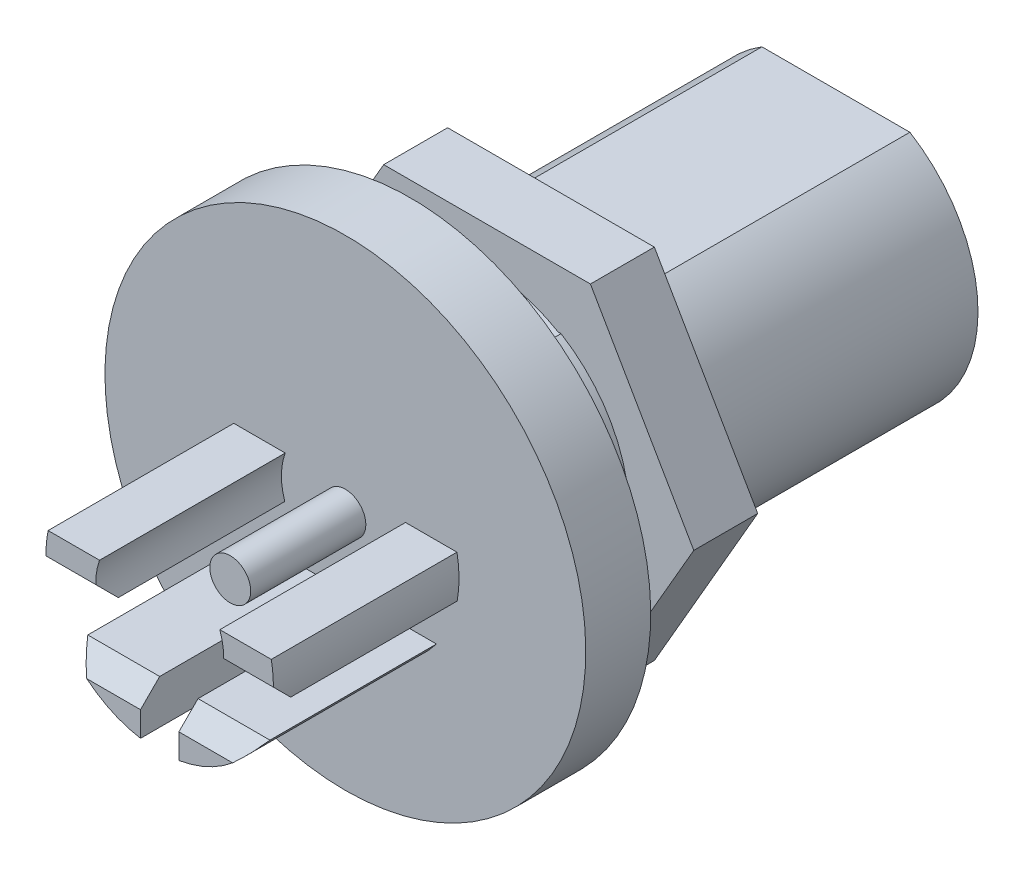
SolidWorks part; units mm, degrees
note: '?' marks a value the reader was unsure of. The reader was unsure of these and kept them because the rebuilt part matched: shared geometry of "Sketch1<3>", "Sketch2<3>".
material "Brass"
ref_plane "Front Plane" through (0, 0, 0) normal (0, 0, 1) x (1, 0, 0)
ref_plane "Top Plane" through (0, 0, 0) normal (0, 1, 0) x (1, 0, 0)
ref_plane "Right Plane" through (0, 0, 0) normal (1, 0, 0) x (0, 0, -1)
ref_axis "Axis1" through (0, 0, -88.99) along (0, 0, 1)?
ref_axis "Axis2" through (0, -55, 0) along (0, 1, 0)?
ref_axis "Axis3" through (-88.99, 0, 0) along (1, 0, 0)?
sketch "Sketch1" plane through (0, 0, 0) normal (1, 0, 0) x (0, 0, -1)
  line L0 (0, 0) -> (5, 0)
  line L1 (5, 0) -> (5, 4)
  line L2 (5, 4) -> (19.18, 4)
  line L3 (19.18, 4) -> (19.18, 5.5562)
  line L4 (19.18, 5.5562) -> (2.54, 5.5562)
  line L5 (2.54, 5.5562) -> (2.54, 6.85)
  line L6 (2.54, 9.4) -> (0, 9.4)
  line L7 (0, 9.4) -> (0, 0)
  line L8 (5, 2) -> (17.18, 2)
  line L9 (17.18, 2) -> (17.18, 0.5)
  line L10 (17.18, 0.5) -> (7, 0.5)
  line L11 (7, 0.5) -> (7, 0)
  line L12 (7, 0) -> (5, 0)
  line L13 (7, 0) -> (19.18, 0) construction
  line L14 (2.54, 8.65) -> (1.71, 8.65)
  line L15 (1.71, 8.65) -> (1.71, 6.85)
  line L16 (1.71, 6.85) -> (2.54, 6.85)
  line L17 (2.54, 8.65) -> (2.54, 9.4)
  line L18 (0, 0) -> (-7.26, 0) construction
  line L19 (0, 0.8) -> (-4.5, 0.8)
  line L20 (-4.5, 0.8) -> (-4.5, 0)
  line L21 (-4.5, 0) -> (0, 0)
  dimension "D1" = 0.83
  dimension "D2" = 16.64
  dimension "D3" = 11.1125
  dimension "D4" = 18.8
  dimension "D5" = 1.8
  dimension "D6" = 0.75
  dimension "D7" = 7.26
  dimension "D8" = 26.44
  dimension "D9" = 8
  dimension "D10" = 1
  dimension "D11" = 4
  dimension "D12" = 2
  dimension "D13" = 2
  dimension "D14" = 1.6
  dimension "D15" = 4.5
  dimension "D16" = 5
revolve "Revolve1" add sketch "Sketch1" angle 360 about L13
revolve "Revolve2" add sketch "Sketch1<3>" angle 360 about L13
sketch "Sketch1<3>" plane through (0, 0, 0) normal (1, 0, 0) x (0, 0, -1) same geometry as "Sketch1"
sketch "Sketch2" plane through (0, 0, 0) normal (0, 0, 1) x (1, 0, 0)
  line L0 (-3.5612, -2.66) -> (-0.75, -2.66)
  line L1 (-0.75, -2.66) -> (-0.75, -4.3813)
  line L2 (0, 0) -> (0, -2.5) construction
  line L3 (0.75, -2.66) -> (0.75, -4.3813)
  line L4 (0.75, -2.66) -> (3.5612, -2.66)
  line L5 (2.3511, 0.85) -> (4.363, 0.85)
  line L6 (0, 0) -> (2.5, 0) construction
  line L7 (2.3685, -0.8) -> (4.3724, -0.8)
  line L8 (-2.3685, -0.8) -> (-4.3724, -0.8)
  line L9 (-2.3511, 0.85) -> (-4.363, 0.85)
  line L10 (-2.3685, -0.8) -> (2.3685, -0.8) construction
  circle A0 centre (0, 0) radius 4.445
  circle A1 centre (0, 0) radius 2.5
  circle A2 centre (0, 0) radius 0.8 construction
  dimension "D1" = 8.89
  dimension "D2" = 5
  dimension "D4" = 1.5
  dimension "D5" = 1.86
  dimension "D6" = 1.65
extrude "Boss-Extrude1" add sketch "Sketch2" along normal blind 7.26 contours A1 L9 A0 L8 | A1 L7 A0 L5
extrude "Boss-Extrude2" add sketch "Sketch2<3>" along normal up to surface (7.26 mm away) contours L0 A0 L1 | L3 A0 L4 up to face at (-3.4181, 0.0255, 7.26)
sketch "Sketch2<3>" plane through (0, 0, 0) normal (0, 0, 1) x (1, 0, 0) same geometry as "Sketch2"
sketch "Sketch3" plane through (0, 0, -19.18) normal (0, 0, -1) x (-1, 0, 0)
  line L0 (-2.8929, 4.7438) -> (2.8929, 4.7438)
  line L1 (0, 0) -> (0, 4.7438) construction
  circle A0 centre (0, 0) radius 5.5562 construction
  circle A1 centre (0, 0) radius 5.5562
  circle M1 centre (0, 0) radius 5.5562
  dimension "D1" = 10.3
extrude "Cut-Extrude1" cut sketch "Sketch3" against normal up to surface (16.64 mm away) contours L0 M1
sketch "Sketch4" plane through (0, 0, 0) normal (1, 0, 0) x (0, 0, -1)
  line L0 (2.54, 6.85) -> (1.71, 6.85)
  line L1 (1.71, -6.85) -> (2.54, -6.85)
  line L2 (1.71, -6.85) -> (2.54, -6.85)
  line L3 (2.54, 6.85) -> (1.71, 6.85) construction
  line L4 (1.71, -8.65) -> (1.71, -6.85)
  line L5 (1.71, 6.85) -> (1.71, 8.65)
  line L6 (1.71, 6.85) -> (1.71, 8.65) construction
  line L7 (1.71, -8.65) -> (1.71, -6.85)
  line L8 (1.71, 8.65) -> (2.54, 8.65)
  line L9 (2.54, -8.65) -> (1.71, -8.65)
  line L10 (2.54, -8.65) -> (1.71, -8.65)
  line L11 (1.71, 8.65) -> (2.54, 8.65) construction
  line L12 (2.5038, 7.75) -> (1.71, 7.75) construction
  line L13 (0, 0) -> (7.8971, 0) construction
  circle A0 centre (2.5038, 7.75) radius 0.7938
  dimension "D1" = 1.5875
revolve "Revolve3" add sketch "Sketch4" angle 360 about L13
chamfer "Chamfer1" distance 0.75 angle 45 4 edges at (2.1556, -2.66, 7.26) (-2.1556, -2.66, 7.26) (3.3705, -0.8, 7.26) (-3.3705, -0.8, 7.26)
sketch "Sketch5" plane through (0, 0, -2.54) normal (0, 0, -1) x (-1, 0, 0)
  line L1 (4.0415, 7) -> (-4.0415, 7)
  line L2 (-4.0415, 7) -> (-8.0829, 0)
  line L3 (-8.0829, 0) -> (-4.0415, -7)
  line L4 (-4.0415, -7) -> (4.0415, -7)
  line L5 (4.0415, -7) -> (8.0829, 0)
  line L6 (8.0829, 0) -> (4.0415, 7)
  circle A0 centre (0, 0) radius 7 construction
  circle A1 centre (0, 0) radius 5.5
  dimension "D2" = 11
  dimension "D1" = 14
extrude "Boss-Extrude3" add sketch "Sketch5" along normal blind 2.5 from offset 3
